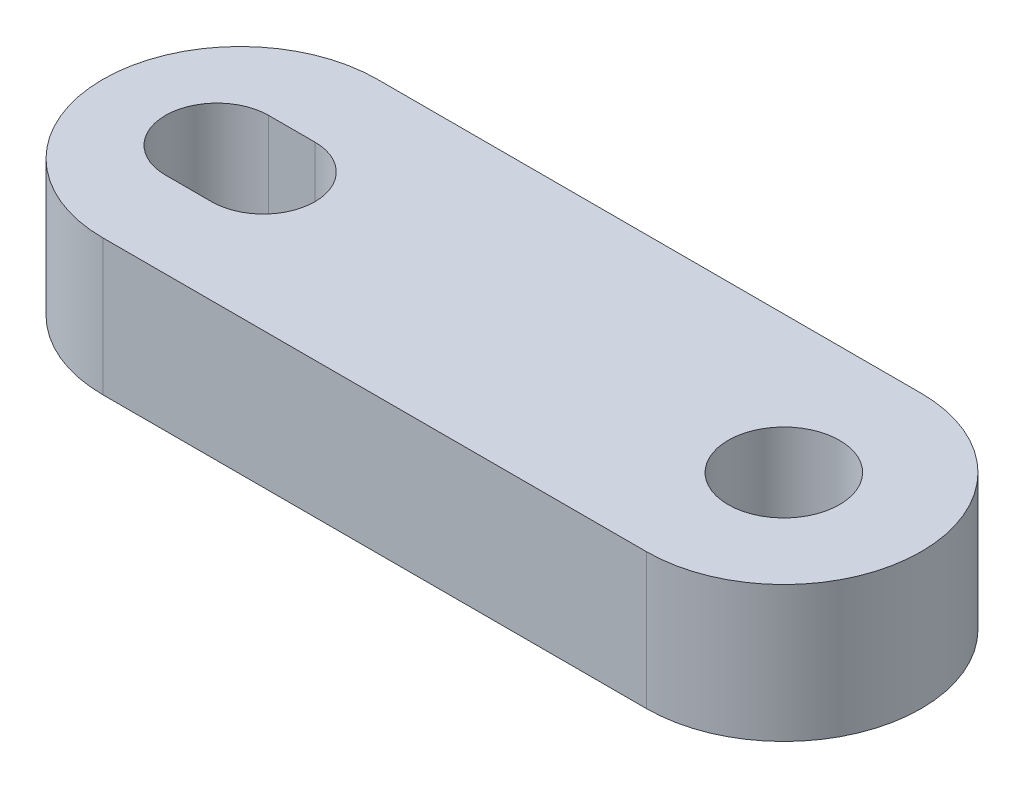
SolidWorks part; units mm, degrees
ref_plane "前基準面" through (0, 0, 0) normal (0, 0, 1) x (1, 0, 0)
ref_plane "上基準面" through (0, 0, 0) normal (0, 1, 0) x (1, 0, 0)
ref_plane "右基準面" through (0, 0, 0) normal (1, 0, 0) x (0, 0, -1)
sketch "草圖1" plane through (0, 0, 0) normal (0, 1, 0) x (1, 0, 0)
  line L0 (-35.9568, 0) -> (39.8148, 0) construction
  line L1 (-10, 0) -> (10, 0) construction
  line L2 (-10, 5.05) -> (10, 5.05)
  line L3 (-10, -5.05) -> (10, -5.05)
  line L4 (-10.85, 0) -> (-9.15, 0) construction
  line L5 (-10.85, 1.9) -> (-9.15, 1.9)
  line L6 (-10.85, -1.9) -> (-9.15, -1.9)
  arc A0 (-10, 5.05) -> (-10, -5.05) centre (-10, 0) ccw
  arc A1 (10, -5.05) -> (10, 5.05) centre (10, 0) ccw
  circle A3 centre (10, 0) radius 2.05
  arc A4 (-10.85, 1.9) -> (-10.85, -1.9) centre (-10.85, 0) ccw
  arc A5 (-9.15, -1.9) -> (-9.15, 1.9) centre (-9.15, 0) ccw
  point P5 (0, 0)
  point P14 (-10, 0)
  point P19 (-6.7405, 0)
  point P20 (0, 0)
  point P21 (-12.75, 0)
  point P22 (-7.25, 0)
  dimension "D2" = 3
  dimension "D3" = 4.1
  dimension "D5" = 3.8
  dimension "D1" = 20
  dimension "D4" = 5.5
extrude "填料-伸長1" add sketch "草圖1" along normal blind 5
sketch "草圖2" plane through (0, 5, 0) normal (0, 1, 0) x (1, 0, 0)
  circle A0 centre (-10, 0) radius 5
